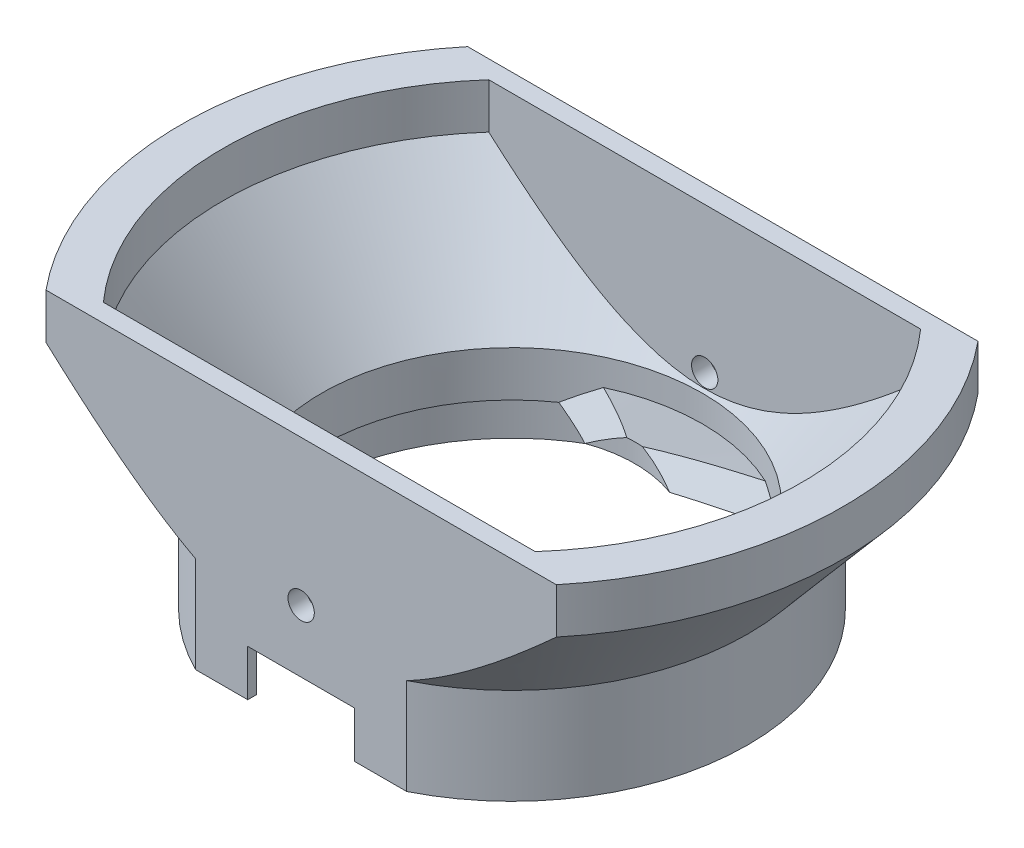
SolidWorks part; units mm, degrees
other "Markup1"
sketch "Sketch12" plane through (-36.5, 26, 23.25) normal (-0.7179, 0.6958, 0.0221) x (0.0006, -0.0311, 0.9995)
ref_plane "Front Plane" through (0, 0, 0) normal (0, 0, 1) x (1, 0, 0)
ref_plane "Top Plane" through (0, 0, 0) normal (0, 1, 0) x (1, 0, 0)
ref_plane "Right Plane" through (0, 0, 0) normal (1, 0, 0) x (0, 0, -1)
sketch "Sketch1" plane through (0, 0, 0) normal (1, 0, 0) x (0, 0, -1)
  line L0 (0, 0) -> (0, 26) construction
  line L1 (-26, 0) -> (-26, 8.5907)
  line L2 (-26, 8.5907) -> (-36.5, 21)
  line L3 (-36.5, 21) -> (-31.9152, 21)
  line L4 (-31.9152, 21) -> (-21, 8.1)
  line L6 (-23.0525, 0) -> (-26, 0)
  line L7 (-23.0525, 0) -> (-23.0525, 3.1)
  line L8 (-36.5, 21) -> (-31.9152, 21)
  line L9 (-36.5, 21) -> (-36.5, 26)
  line L10 (-36.5, 26) -> (-31.9152, 26)
  line L11 (-31.9152, 21) -> (-31.9152, 26)
  line L12 (-23.0525, 3.1) -> (-21, 3.1)
  line L13 (-21, 3.1) -> (-21, 8.1)
  dimension "D1" = 3.5
  dimension "D2" = 26
  dimension "D3" = 23.0525
  dimension "D4" = 36.5
  dimension "D5" = 5
  dimension "D6" = 26
  dimension "D7" = 21
  dimension "D8" = 3.1
  dimension "D9" = 5
revolve "Revolve1" add sketch "Sketch1" angle 360 about L0 region at (0, 10.8751, 26.9281) region at (0, 23.5, 34.2076)
sketch "Sketch2" plane through (0, 0, 0) normal (0, -1, 0) x (1, 0, 0)
  line L1 (-28.1369, -23.25) -> (28.1369, -23.25)
  line L2 (-28.1369, -23.25) -> (-28.1369, -36.5)
  line L3 (-28.1369, -36.5) -> (28.1369, -36.5)
  line L4 (28.1369, -23.25) -> (28.1369, -36.5)
  line L5 (-28.1369, 23.25) -> (28.1369, 23.25)
  line L6 (-28.1369, 23.25) -> (-28.1369, 36.5)
  line L7 (-28.1369, 36.5) -> (28.1369, 36.5)
  line L8 (28.1369, 23.25) -> (28.1369, 36.5)
  circle A0 centre (0, 0) radius 26 construction
  circle A1 centre (0, 0) radius 36.5 construction
  circle A2 centre (0, 0) radius 36.5 construction
  point P5 (0, -23.25)
  dimension "D1" = 23.25
extrude "Cut-Extrude1" cut sketch "Sketch2" against normal through all
sketch "Sketch6" plane through (0, 26, 0) normal (0, 1, 0) x (1, 0, 0)
  line L0 (28.1369, 23.25) -> (-28.1369, 23.25)
  line L1 (-28.1369, 23.25) -> (-28.1369, 21.25)
  line L2 (-28.1369, 21.25) -> (28.1369, 21.25)
  line L3 (28.1369, 21.25) -> (28.1369, 23.25)
  line L5 (-28.1369, -23.25) -> (28.1369, -23.25)
  line L6 (-28.1369, -23.25) -> (-28.1369, -21.25)
  line L7 (-28.1369, -21.25) -> (28.1369, -21.25)
  line L8 (28.1369, -23.25) -> (28.1369, -21.25)
  dimension "D1" = 2
extrude "Boss-Extrude2" add sketch "Sketch6" against normal up to surface (1.0473 mm away) up to face at (0, 15.9992, 0)
sketch "Sketch3" plane through (0, 0, 0) normal (0, -1, 0) x (1, 0, 0)
  line L0 (-11.6378, 23.25) -> (11.6378, 23.25) construction
  line L1 (-5.89, -23.25) -> (5.89, -23.25)
  line L2 (-5.89, -23.25) -> (-5.89, -22.2873)
  line L3 (-5.89, -22.2873) -> (5.89, -22.2873)
  line L4 (5.89, -23.25) -> (5.89, -22.2873)
  line L5 (11.6378, -23.25) -> (-11.6378, -23.25) construction
  line L6 (5.89, 23.25) -> (-5.89, 23.25)
  line L7 (5.89, 23.25) -> (5.89, 22.2873)
  line L8 (5.89, 22.2873) -> (-5.89, 22.2873)
  line L9 (-5.89, 23.25) -> (-5.89, 22.2873)
  circle A0 centre (0, 0) radius 23.0525 construction
  point P6 (0, -22.2873)
  point P16 (0, 22.2873)
  dimension "D1" = 11.78
extrude "Cut-Extrude2" cut sketch "Sketch3" against normal up to surface (3.1 mm away) up to face at (0, 3.1, -21)
ref_plane "Plane1" through (0, 4, 0) normal (0, -1, 0) x (-1, 0, 0)
sketch "Sketch4" plane through (0, 3.1, 0) normal (0, -1, 0) x (-1, 0, 0)
  line L0 (7, 19.799) -> (7, 9.799)
  line L1 (7, 9.799) -> (-7, 9.799)
  line L2 (-7, 9.799) -> (-7, 19.799)
  line L3 (2.7392, -11.7268) -> (-1.0703, -20.9727)
  line L4 (2.7392, -11.7268) -> (-10.2051, -6.3934)
  line L5 (-10.2051, -6.3934) -> (-14.0146, -15.6394)
  line L6 (0, 0) -> (-8, -19.4165) construction
  line L7 (7, 19.799) -> (7, 21.964)
  line L8 (-7, 19.799) -> (-7, 21.964)
  line L9 (-1.0703, -20.9727) -> (-1.8951, -22.9745)
  line L10 (-14.0146, -15.6394) -> (-14.8394, -17.6411)
  circle A0 centre (0, 0) radius 21 construction
  circle A1 centre (0, 0) radius 23.0525
  circle A2 centre (0, 0) radius 23.0525 construction
  point P12 (-3.7329, -9.0601)
  circle M25 centre (0, 0) radius 21
  dimension "D1" = 14
  dimension "D2" = 10
  dimension "D3" = 8
extrude "Boss-Extrude1" [suppressed] add sketch "Sketch4" against normal blind 3 from surface contours L2 L1 L0 M25 starting at plane "Plane1"
mirror "Mirror4" [suppressed] about plane through (0, 0, 0) normal (0, 0, 1)
draft "Draft2" [suppressed] type of draft neutral plane draft angle 50 faces to draft 6 reverse direction yes parameters "D1"=50
fillet "Fillet2" [suppressed] radius 2
sketch "Sketch7" plane through (0, 0, -23.25) normal (0, 0, -1) x (-1, 0, 0)
  line L1 (5.89, 3.1) -> (-5.89, 3.1) construction
  circle A0 centre (0, 9.95) radius 1.45
  dimension "D1" = 2.9
  dimension "D2" = 6.85
extrude "Cut-Extrude3" cut sketch "Sketch7" against normal through all
sketch "Sketch9" plane through (0, 0, 0) normal (1, 0, 0) x (0, 0, -1)
  line L0 (21, 3.1) -> (10.3758, 5.9507)
  line L1 (10.3758, 5.9507) -> (10.8941, 7.8824)
  line L2 (10.8941, 7.8824) -> (21.5183, 5.0317)
  line L3 (21.5183, 5.0317) -> (21, 3.1)
  line L4 (21, 3.1) -> (21, 5.3493) construction
  line L5 (-23.0525, 3.1) -> (23.0525, 3.1) construction
  line L6 (-21, 3.1) -> (21, 3.1) construction
  line L7 (21, 3.1) -> (21, 8.1) construction
  line L8 (21, 3.1) -> (16.054, 3.1) construction
  line L9 (10.8941, 7.8824) -> (21.5183, 8.1)
  line L10 (21.5183, 8.1) -> (21.5183, 5.0317)
  line L11 (21, 8.1) -> (-21, 8.1) construction
  line L12 (0, 0) -> (0, 27.7883) construction
  dimension "D1" = 11
  dimension "D2" = 2
  dimension "D4" = 15.02
revolve "Revolve2" add sketch "Sketch9" angle 70 mid plane about L12 region at (0, 5.4912, -15.9471)
mirror "Mirror3" about plane through (0, 0, 0) normal (0, 0, 1) of "Revolve2"
ref_plane "Plane3" through (0, 0, 0) normal (0.9246, 0, -0.381) x (0.381, 0, 0.9246)
sketch "Sketch13" plane through (0, 0, 0) normal (0, -1, 0) x (1, 0, 0)
  line L0 (-5.89, -23.25) -> (-5.89, -22.2873) construction
  line L1 (-5.89, 22.2873) -> (-5.89, 23.25) construction
  line L2 (-5.89, 23.25) -> (-11.6378, 23.25) construction
  line L3 (-11.6378, -23.25) -> (-5.89, -23.25) construction
  line L4 (5.89, -22.2873) -> (5.89, -23.25) construction
  line L5 (5.89, -23.25) -> (11.6378, -23.25) construction
  line L6 (11.6378, 23.25) -> (5.89, 23.25) construction
  line L7 (5.89, 23.25) -> (5.89, 22.2873) construction
  line L8 (-5.89, -23.25) -> (-5.89, -22.2873)
  line L9 (-5.89, 22.2873) -> (-5.89, 23.25)
  line L10 (-5.89, 23.25) -> (-11.6378, 23.25)
  line L11 (-11.6378, -23.25) -> (-5.89, -23.25)
  line L12 (5.89, -22.2873) -> (5.89, -23.25)
  line L13 (5.89, -23.25) -> (11.6378, -23.25)
  line L14 (11.6378, 23.25) -> (5.89, 23.25)
  line L15 (5.89, 23.25) -> (5.89, 22.2873)
  arc A0 (-5.89, 22.2873) -> (-5.89, -22.2873) centre (0, 0) ccw construction
  arc A1 (-11.6378, 23.25) -> (-11.6378, -23.25) centre (0, 0) ccw construction
  arc A2 (11.6378, -23.25) -> (11.6378, 23.25) centre (0, 0) ccw construction
  arc A3 (5.89, -22.2873) -> (5.89, 22.2873) centre (0, 0) ccw construction
  arc A4 (-5.89, 22.2873) -> (-5.89, -22.2873) centre (0, 0) ccw
  arc A5 (-11.6378, 23.25) -> (-11.6378, -23.25) centre (0, 0) ccw
  arc A6 (11.6378, -23.25) -> (11.6378, 23.25) centre (0, 0) ccw
  arc A7 (5.89, -22.2873) -> (5.89, 22.2873) centre (0, 0) ccw
extrude "Boss-Extrude5" add sketch "Sketch13" along normal blind 2
mirror "Mirror2" about plane through (0, 0, 0) normal (0, 0, 1) of "Cut-Extrude3"
sketch "Sketch16" plane through (0, 3.1, 0) normal (0, -1, 0) x (1, 0, 0)
  circle A0 centre (0, 0) radius 13.25 construction
  circle A1 centre (0, 0) radius 13.55
  dimension "D1" = 26.5
  dimension "D2" = 0.3
extrude "Cut-Extrude6" cut sketch "Sketch16" against normal through all
sketch "Sketch14" [suppressed] plane through (0, 3.1, 0) normal (0, -1, 0) x (1, 0, 0)
  line L32 (-20.4284, 4.8662) -> (-13.5215, 0.8784)
  line L33 (-19.6822, 7.3221) -> (-13.0864, 3.514)
  line L42 (-7.5215, 11.2707) -> (-14.4284, 15.2585)
  line L43 (-9.5864, 9.5762) -> (-16.1822, 13.3842)
  line L52 (-12.9904, 7.5) -> (-18.1865, 10.5) construction
  line L53 (-16.3843, 5.418) -> (-12.8843, 11.4802) construction
  line L62 (-14.7404, 4.4689) -> (-11.2404, 10.5311)
  line L63 (-6, 20.1246) -> (-6, 12.1492)
  line L72 (-3.5, 20.7063) -> (-3.5, 13.0902)
  line L73 (6, 12.1492) -> (6, 20.1246)
  line L82 (3.5, 13.0902) -> (3.5, 20.7063)
  line L83 (-3.5, 15) -> (3.5, 15)
  line L84 (0, 15) -> (0, 21) construction
  line L85 (-3.5, 16.8982) -> (3.5, 16.8982) construction
  line L86 (14.4284, 15.2585) -> (7.5215, 11.2707)
  line L87 (16.1822, 13.3842) -> (9.5864, 9.5762)
  line L88 (13.5215, 0.8784) -> (20.4284, 4.8662)
  line L89 (13.0864, 3.514) -> (19.6822, 7.3221)
  line L90 (11.2404, 10.5311) -> (14.7404, 4.4689)
  line L91 (12.9904, 7.5) -> (18.1865, 10.5) construction
  line L92 (12.8843, 11.4802) -> (16.3843, 5.418) construction
  line L93 (20.4284, -4.8662) -> (13.5215, -0.8784)
  line L94 (19.6822, -7.3221) -> (13.0864, -3.514)
  line L95 (7.5215, -11.2707) -> (14.4284, -15.2585)
  line L96 (9.5864, -9.5762) -> (16.1822, -13.3842)
  line L97 (14.7404, -4.4689) -> (11.2404, -10.5311)
  line L98 (12.9904, -7.5) -> (18.1865, -10.5) construction
  line L99 (16.3843, -5.418) -> (12.8843, -11.4802) construction
  line L100 (6, -20.1246) -> (6, -12.1492)
  line L101 (3.5, -20.7063) -> (3.5, -13.0902)
  line L102 (-6, -12.1492) -> (-6, -20.1246)
  line L103 (-3.5, -13.0902) -> (-3.5, -20.7063)
  line L104 (3.5, -15) -> (-3.5, -15)
  line L105 (0, -15) -> (0, -21) construction
  line L106 (3.5, -16.8982) -> (-3.5, -16.8982) construction
  line L107 (-14.4284, -15.2585) -> (-7.5215, -11.2707)
  line L108 (-16.1822, -13.3842) -> (-9.5864, -9.5762)
  line L109 (-13.5215, -0.8784) -> (-20.4284, -4.8662)
  line L110 (-13.0864, -3.514) -> (-19.6822, -7.3221)
  line L111 (-11.2404, -10.5311) -> (-14.7404, -4.4689)
  line L112 (-12.9904, -7.5) -> (-18.1865, -10.5) construction
  line L113 (-12.8843, -11.4802) -> (-16.3843, -5.418) construction
  arc A23 (-14.4284, 15.2585) -> (-20.4284, 4.8662) centre (0, 0) ccw construction
  arc A24 (-7.5215, 11.2707) -> (-13.5215, 0.8784) centre (0, 0) ccw construction
  circle A25 centre (0, 0) radius 21 construction
  arc A26 (-7.5215, 11.2707) -> (-13.5215, 0.8784) centre (0, 0) ccw
  arc A27 (-14.4284, 15.2585) -> (-16.1822, 13.3842) centre (0, 0) ccw
  arc A28 (-19.6822, 7.3221) -> (-20.4284, 4.8662) centre (0, 0) ccw
  arc A29 (6, 12.1492) -> (-6, 12.1492) centre (0, 0) ccw
  arc A30 (6, 20.1246) -> (3.5, 20.7063) centre (0, 0) ccw
  arc A31 (-3.5, 20.7063) -> (-6, 20.1246) centre (0, 0) ccw
  arc A32 (13.5215, 0.8784) -> (7.5215, 11.2707) centre (0, 0) ccw
  arc A33 (20.4284, 4.8662) -> (19.6822, 7.3221) centre (0, 0) ccw
  arc A34 (16.1822, 13.3842) -> (14.4284, 15.2585) centre (0, 0) ccw
  arc A35 (7.5215, -11.2707) -> (13.5215, -0.8784) centre (0, 0) ccw
  arc A36 (14.4284, -15.2585) -> (16.1822, -13.3842) centre (0, 0) ccw
  arc A37 (19.6822, -7.3221) -> (20.4284, -4.8662) centre (0, 0) ccw
  arc A38 (-6, -12.1492) -> (6, -12.1492) centre (0, 0) ccw
  arc A39 (-6, -20.1246) -> (-3.5, -20.7063) centre (0, 0) ccw
  arc A40 (3.5, -20.7063) -> (6, -20.1246) centre (0, 0) ccw
  arc A41 (-13.5215, -0.8784) -> (-7.5215, -11.2707) centre (0, 0) ccw
  arc A42 (-20.4284, -4.8662) -> (-19.6822, -7.3221) centre (0, 0) ccw
  arc A43 (-16.1822, -13.3842) -> (-14.4284, -15.2585) centre (0, 0) ccw
  point P19 (-14.6343, 8.4491)
  point P114 (0, 0)
  dimension "D1" = 7
  dimension "D2" = 6
extrude "Cut-Extrude8" [suppressed] cut sketch "Sketch14" against normal through all
draft "Draft11" type of draft neutral plane draft angle 60 faces to draft 4 face at (9.9085, 5.1349, 14.1509) face at (-9.9085, 5.1349, 14.1509) face at (9.9085, 5.1349, -14.1509) face at (-9.9085, 5.1349, -14.1509) neutral plane through (0, 3.1, 0) neutral plane normal (0, -1, 0) reverse direction yes parameters "D1"=60
